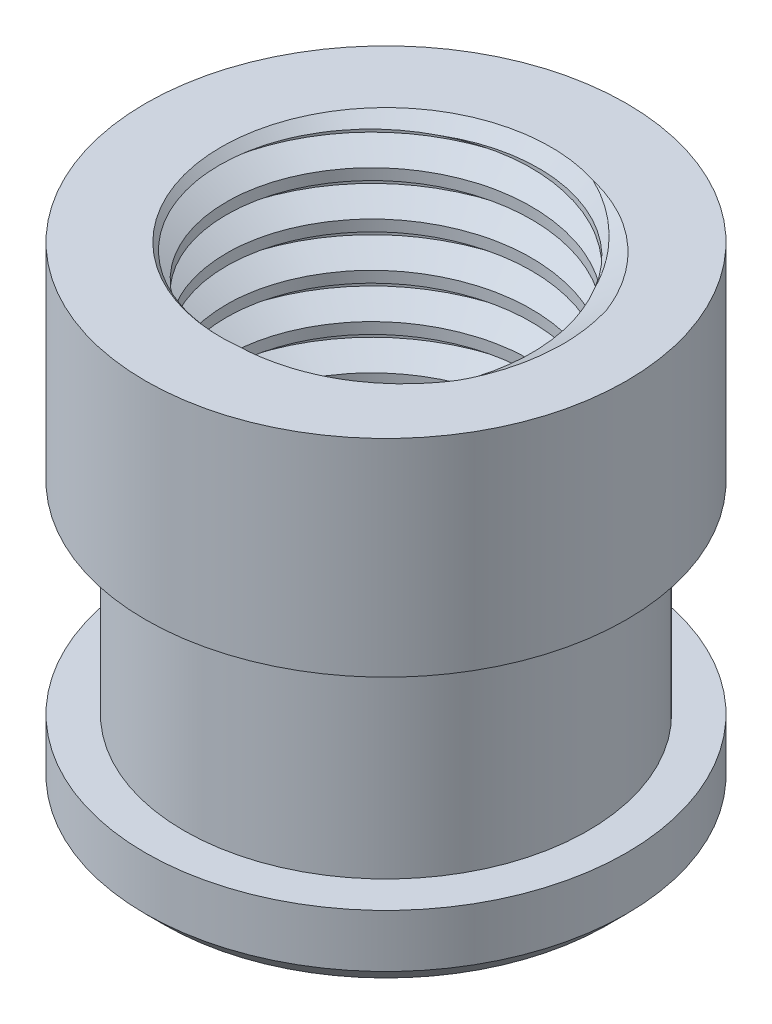
SolidWorks part; units mm, degrees
material "1060 Alloy"
ref_plane "Front Plane" through (0, 0, 0) normal (0, 0, 1) x (1, 0, 0)
ref_plane "Top Plane" through (0, 0, 0) normal (0, 1, 0) x (1, 0, 0)
ref_plane "Right Plane" through (0, 0, 0) normal (1, 0, 0) x (0, 0, -1)
sketch "Sketch1" plane through (0, 0, 0) normal (0, 1, 0) x (1, 0, 0)
  circle A0 centre (0, 0) radius 12.5
  dimension "D1" = 25
extrude "Boss-Extrude1" add sketch "Sketch1" along normal blind 25
hole_wizard "5/8 (0.625) Diameter Hole1" positions "3DSketch3" profile "Sketch3" hole size "5/8" standard "ANSI Inch"
sketch3d "3DSketch3"
  line L0 (0, 25, 0) -> (0, 0, 0) construction
  point P0 (0, 0, 0)
  point P3 (0, 0, 0)
  point P6 (0, 25, 0)
sketch "Sketch3" plane through (0, 25, 0) normal (1, 0, 0) x (0, 0, 1)
  line L0 (0, 0) -> (0, 22.7693)
  line L1 (0, 22.7693) -> (7.9375, 18)
  line L2 (7.9375, 18) -> (7.9375, 0.635)
  line L3 (7.9375, 0.635) -> (8.5725, 0)
  line L5 (8.5725, 0) -> (0, 0)
  line L6 (-7.9375, 0.635) -> (-8.5725, 0) construction
  line L10 (0, 22.7693) -> (-7.9375, 18) construction
  line L11 (0, -6.35) -> (0, 107.95) construction
  dimension "Hole Dia." = 15.875
  dimension "Hole Depth" = 18
  dimension "Near C'Sink Dia." = 17.145
  dimension "Near C'Sink Angle" = 90
  dimension "Drill Angle" = 118
sketch "Sketch4" plane through (0, 0, 0) normal (0, 0, 1) x (1, 0, 0)
  line L0 (12.5, 8) -> (12.5, 10) construction
  line L1 (14.5, 3.75) -> (10.5, 3.75)
  line L2 (14.5, 3.75) -> (14.5, 12.25)
  line L3 (14.5, 12.25) -> (10.5, 12.25)
  line L4 (10.5, 3.75) -> (10.5, 12.25)
  line L5 (14.5, 3.75) -> (10.5, 12.25) construction
  line L6 (14.5, 12.25) -> (10.5, 3.75) construction
  line L7 (14.5, 5.75) -> (10.5, 5.75)
  line L8 (14.5, 5.75) -> (14.5, 14.25)
  line L9 (14.5, 14.25) -> (10.5, 14.25)
  line L10 (10.5, 5.75) -> (10.5, 14.25)
  line L11 (14.5, 5.75) -> (10.5, 14.25) construction
  line L12 (14.5, 14.25) -> (10.5, 5.75) construction
  line L14 (-12.5, 0) -> (12.5, 0) construction
  point P0 (12.5, 8)
  point P5 (12.5, 10)
  dimension "D1" = 12.5
  dimension "D2" = 8.5
  dimension "D3" = 8.5
  dimension "D4" = 8
  dimension "D5" = 10
  dimension "D6" = 4
  dimension "D7" = 4
ref_axis "Axis1" through (0, 25, 0) along (0, -1, 0)
revolve "Cut-Revolve1" cut sketch "Sketch4" angle 360 about axis through (0, 25, 0) along (0, -1, 0)
chamfer "Chamfer1" distance 1 angle 45 1 edges at (0, 0, 12.5)
thread "Thread1" pitch 2.3091 method cut profile "Thread Profile1" start angle 0, offset 5, length 18, pitch 2.3091, diameter 15.875
ref_plane "Plane1" through (-7.9375, 29.365, 0) normal (0, 0, 1) x (-1, 0, 0)
sketch "Thread Profile1" plane through (-7.9375, 29.365, 0) normal (0, 0, 1) x (-1, 0, 0)
  line L0 (0, 0) -> (0, 2.3091) construction
  line L1 (0, 0) -> (1.2498, 0.7216)
  line L2 (1.2498, 0.7216) -> (1.2498, 1.0102)
  line L3 (1.2498, 1.0102) -> (0, 1.7318)
  line L4 (1.2498, 0.8659) -> (0, 0.8659) construction
  line L11 (0, 0) -> (0, 1.7318)
  point P2 (0, 0)
  dimension "Pitch" = 2.3091
  dimension "Profile_Angle" = 60
  dimension "Profile_Land" = 0.2886
  dimension "Profile_Height" = 1.2498
